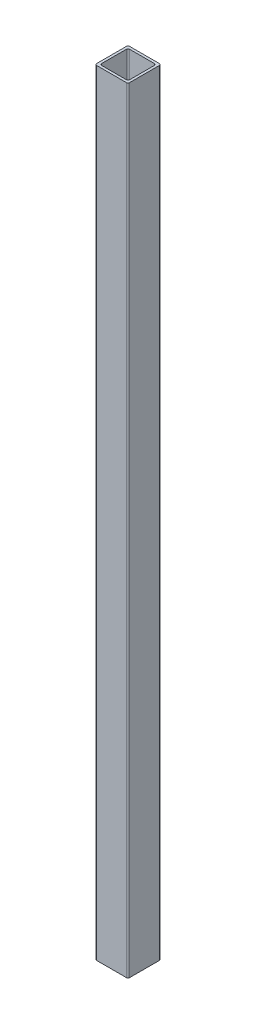
SolidWorks part; units mm, degrees
material "Hexcel AS4C (3000 Filaments)"
ref_plane "Front Plane" through (0, 0, 0) normal (0, 0, 1) x (1, 0, 0)
ref_plane "Top Plane" through (0, 0, 0) normal (0, 1, 0) x (1, 0, 0)
ref_plane "Right Plane" through (0, 0, 0) normal (1, 0, 0) x (0, 0, -1)
sketch "Sketch1" plane through (0, 0, 0) normal (0, 1, 0) x (1, 0, 0)
  line L1 (-9, -10) -> (9, -10)
  line L2 (-10, -9) -> (-10, 9)
  line L3 (-9, 10) -> (9, 10)
  line L4 (10, -9) -> (10, 9)
  line L5 (-10, -10) -> (10, 10) construction
  line L6 (-10, 10) -> (10, -10) construction
  line L7 (-7.5, -8.5) -> (7.5, -8.5)
  line L8 (-8.5, -7.5) -> (-8.5, 7.5)
  line L9 (-7.5, 8.5) -> (7.5, 8.5)
  line L10 (8.5, -7.5) -> (8.5, 7.5)
  line L11 (-8.5, -8.5) -> (8.5, 8.5) construction
  line L12 (-8.5, 8.5) -> (8.5, -8.5) construction
  arc A0 (-9, -10) -> (-10, -9) centre (-9, -9) cw
  arc A1 (9, 10) -> (10, 9) centre (9, 9) cw
  arc A2 (9, -10) -> (10, -9) centre (9, -9) ccw
  arc A3 (-10, 9) -> (-9, 10) centre (-9, 9) cw
  arc A4 (-7.5, -8.5) -> (-8.5, -7.5) centre (-7.5, -7.5) cw
  arc A5 (7.5, -8.5) -> (8.5, -7.5) centre (7.5, -7.5) ccw
  arc A6 (7.5, 8.5) -> (8.5, 7.5) centre (7.5, 7.5) cw
  arc A7 (-8.5, 7.5) -> (-7.5, 8.5) centre (-7.5, 7.5) cw
  point P0 (0, 0)
  point P18 (0, 0)
  dimension "D3" = 1
  dimension "D6" = 1
  dimension "D7" = 1
  dimension "D8" = 1
  dimension "D9" = 1
  dimension "D1" = 20
  dimension "D2" = 20
  dimension "D4" = 17
  dimension "D5" = 17
extrude "Boss-Extrude1" add sketch "Sketch1" along normal blind 470
